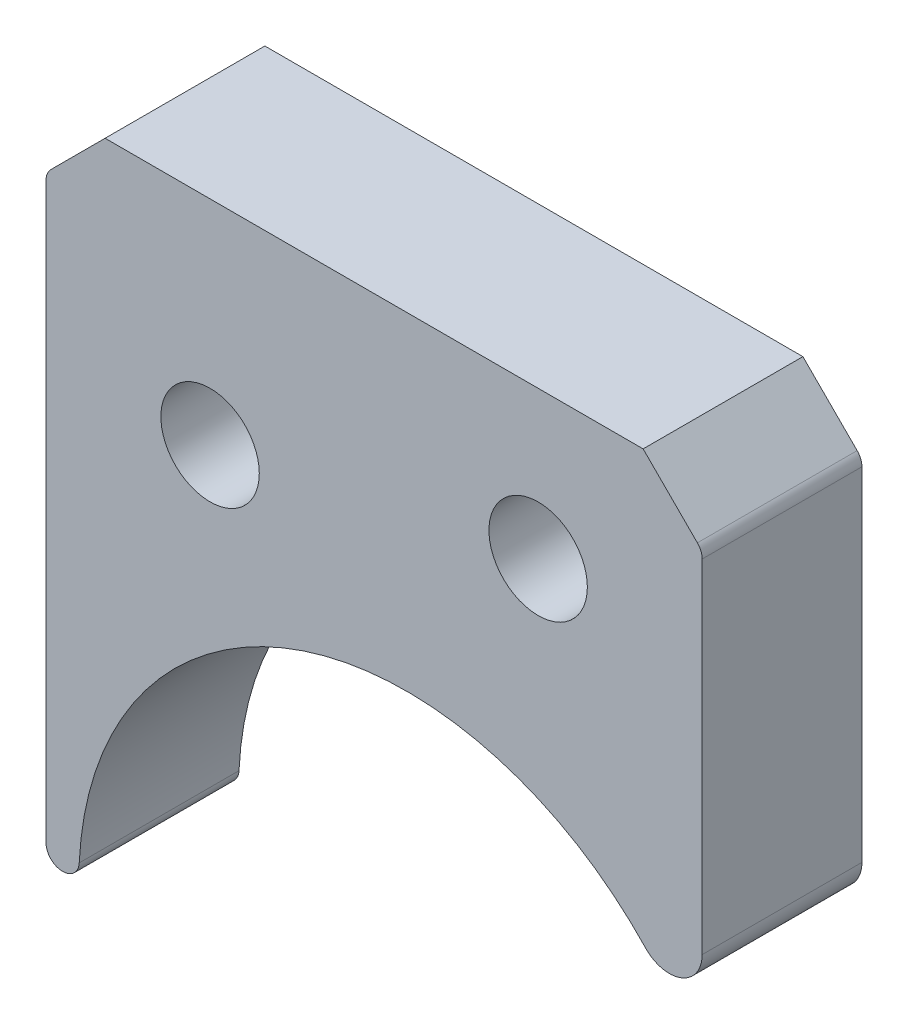
SolidWorks part; units mm, degrees
ref_plane "Front Plane" through (0, 0, 0) normal (0, 0, 1) x (1, 0, 0)
ref_plane "Top Plane" through (0, 0, 0) normal (0, 1, 0) x (1, 0, 0)
ref_plane "Right Plane" through (0, 0, 0) normal (1, 0, 0) x (0, 0, -1)
sketch "Sketch1" plane through (0, 0, 0) normal (0, 0, 1) x (1, 0, 0)
  line L1 (0, 0) -> (1, 0)
  line L2 (0, 0) -> (0, 20)
  line L3 (0, 20) -> (20, 20)
  line L4 (20, 4.3589) -> (20, 20)
  arc A0 (20, 4.3589) -> (1, 0) centre (11, 0) ccw
extrude "Boss-Extrude1" add sketch "Sketch1" along normal blind 4.87
sketch "Sketch2" plane through (0, 0, 4.87) normal (0, 0, 1) x (1, 0, 0)
  line L0 (5, 15.5) -> (11, 15.5) construction
  line L1 (11, 15.5) -> (15, 15.5) construction
  line L2 (11, 15.5) -> (11, 0) construction
  line L3 (5, 15.5) -> (5, 13.5) construction
  circle A0 centre (5, 13.5) radius 1.5
  circle A1 centre (15, 15.5) radius 1.5
  point P7 (0, 0)
extrude "Cut-Extrude1" cut sketch "Sketch2" against normal blind 4.87
chamfer "Chamfer1" distance 1.8 angle 45 2 edges at (0, 20, 2.435) (20, 20, 2.435)
fillet "Fillet1" radius 0.5 4 edges at (0, 0, 2.435) (1, 0, 2.435) (20, 18.2, 2.435) (0, 18.2, 2.435)
fillet "Fillet2" radius 1 1 edges at (20, 4.3589, 2.435)
